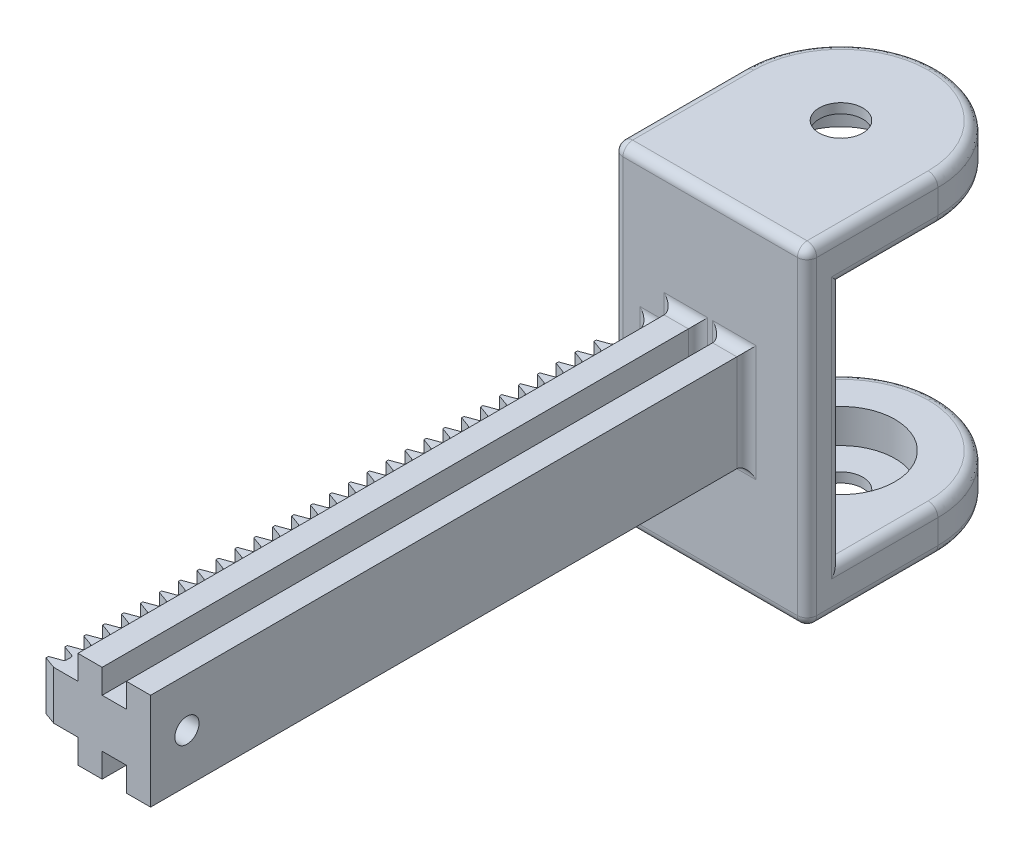
SolidWorks part; units mm, degrees
note: The reader was unsure of these and kept them because the rebuilt part matched: shared geometry of "Croquis4<4>".
ref_plane "Alzado" through (0, 0, 0) normal (1, 0, 0) x (0, 1, 0)
ref_plane "Planta" through (0, 0, 0) normal (0, 0, 1) x (0, 1, 0)
ref_plane "Vista lateral" through (0, 0, 0) normal (0, 1, 0) x (-1, 0, 0)
sketch "Croquis2" plane through (0, 0, 0) normal (0, 0, 1) x (0, 1, 0)
  line L0 (34, -20) -> (34, 20)
  line L1 (-34, -20) -> (34, -20)
  line L2 (-34, -20) -> (-34, 20)
  line L3 (-34, 20) -> (34, 20)
  line L5 (-34, -20) -> (34, 20) construction
  line L6 (-34, 20) -> (34, -20) construction
  point P0 (0, 0)
  point P1 (0, -20)
  point P13 (34, 0)
  dimension "D2" = 68
  dimension "D3" = 40
extrude "Saliente-Extruir1" add sketch "Croquis2" along normal blind 7
sketch "Croquis3" plane through (0, 0, 0) normal (0, 0, -1) x (1, 0, 0)
  line L0 (20, -34) -> (-20, -34) construction
  line L1 (20, 34) -> (-20, 34) construction
  line L2 (20, -34) -> (-20, -34)
  line L3 (20, 34) -> (-20, 34)
  line L4 (-20, 34) -> (-20, 25)
  line L5 (-20, 34) -> (-20, -34) construction
  line L6 (-20, 25) -> (20, 25)
  line L7 (20, 34) -> (20, -34) construction
  line L8 (20, 25) -> (20, 34)
  line L9 (20, -34) -> (20, -25)
  line L10 (20, -25) -> (-20, -25)
  line L11 (-20, -25) -> (-20, -34)
  dimension "D1" = 9
  dimension "D2" = 9
extrude "Saliente-Extruir2" add sketch "Croquis3" along normal blind 40
sketch "Croquis4" plane through (0, 25, 0) normal (0, -1, 0) x (1, 0, 0)
  line L0 (20, -20) -> (0, -20) construction
  line L1 (20, -40) -> (20, 0) construction
  line L2 (0, -20) -> (0, 0) construction
  circle A0 centre (0, -20) radius 11.15
  circle A1 centre (0, -20) radius 4.5
  dimension "D1" = 22.3
  dimension "D2" = 9
extrude "Cortar-Extruir1" cut sketch "Croquis4" against normal blind 7 and the other way offset from surface (57 mm away) 2 contours A1 | A0 A1 other way up to face at (0, -34, -16.5)
extrude "Cortar-Extruir2" cut sketch "Croquis4<4>" against normal up to next and the other way up to next contours A1
sketch "Croquis4<4>" plane through (0, 25, 0) normal (0, -1, 0) x (1, 0, 0) same geometry as "Croquis4"
sketch "Croquis5" plane through (0, 0, 7) normal (0, 0, 1) x (1, 0, 0)
  line L0 (-12.5, -5) -> (-7.5, -5)
  line L1 (7.5, -10) -> (2.5, -10)
  line L2 (7.5, -10) -> (7.5, 10)
  line L3 (7.5, 10) -> (2.5, 10)
  line L4 (-7.5, -10) -> (-7.5, -5)
  line L5 (7.5, -10) -> (-7.5, 10) construction
  line L6 (7.5, 10) -> (-7.5, -10) construction
  line L7 (-12.5, -5) -> (-12.5, 5)
  line L9 (-12.5, 5) -> (-7.5, 5)
  line L10 (-12.5, -5) -> (-7.5, 5) construction
  line L11 (-7.5, -5) -> (-12.5, 5) construction
  line L12 (-7.5, 5) -> (-7.5, 10)
  line L13 (-2.5, 10) -> (-7.5, 10)
  line L15 (-2.5, 10) -> (-2.5, 5)
  line L16 (-2.5, 5) -> (2.5, 5)
  line L17 (2.5, 10) -> (2.5, 5)
  line L18 (55, 0) -> (-55, 0) construction
  line L19 (2.5, -10) -> (2.5, -5)
  line L20 (-2.5, -5) -> (2.5, -5)
  line L21 (-2.5, -10) -> (-2.5, -5)
  line L22 (-2.5, -10) -> (-7.5, -10)
  point P0 (0, 0)
  point P5 (0, 5)
  point P7 (-10, 0)
  dimension "D1" = 20
  dimension "D2" = 15
  dimension "D3" = 5
  dimension "D4" = 10
  dimension "D5" = 5
  dimension "D6" = 5
extrude "Saliente-Extruir3" add sketch "Croquis5" along normal blind 123
sketch "Croquis8" plane through (0, 0, 0) normal (0, 1, 0) x (-1, 0, 0)
  line L0 (12.5, 130) -> (12.5, 7) construction
  line L1 (12.5, 130) -> (12.5, 7)
  line L2 (12.5, 130) -> (15, 129.0901)
  line L3 (15, 129.0901) -> (15, 128.6099)
  line L4 (15, 128.6099) -> (12.5, 127.7)
  line L5 (12.5, 127.7) -> (12.5, 126.1)
  line L6 (13.75, 128.155) -> (13.75, 129.545) construction
  line L7 (12.5, 126.9) -> (10.9627, 126.9) construction
  line L8 (12.5, 116) -> (12.5, 114.4)
  line L9 (12.5, 126.1) -> (15, 125.1901)
  line L10 (15, 125.1901) -> (15, 124.7099)
  line L11 (15, 124.7099) -> (12.5, 123.8)
  line L12 (12.5, 123.8) -> (12.5, 122.2)
  line L13 (13.75, 124.255) -> (13.75, 125.645) construction
  line L14 (15, 116.9099) -> (12.5, 116)
  line L15 (15, 117.3901) -> (15, 116.9099)
  line L16 (12.5, 118.3) -> (15, 117.3901)
  line L17 (12.5, 119.9) -> (12.5, 118.3)
  line L18 (15, 120.8099) -> (12.5, 119.9)
  line L19 (15, 121.2901) -> (15, 120.8099)
  line L20 (12.5, 122.2) -> (15, 121.2901)
  line L21 (12.5, 108.2) -> (12.5, 106.6)
  line L22 (15, 109.1099) -> (12.5, 108.2)
  line L23 (15, 109.5901) -> (15, 109.1099)
  line L24 (12.5, 110.5) -> (15, 109.5901)
  line L25 (12.5, 112.1) -> (12.5, 110.5)
  line L26 (15, 113.0099) -> (12.5, 112.1)
  line L27 (15, 113.4901) -> (15, 113.0099)
  line L28 (12.5, 114.4) -> (15, 113.4901)
  line L29 (12.5, 100.4) -> (12.5, 98.8)
  line L30 (15, 101.3099) -> (12.5, 100.4)
  line L31 (15, 101.7901) -> (15, 101.3099)
  line L32 (12.5, 102.7) -> (15, 101.7901)
  line L33 (12.5, 104.3) -> (12.5, 102.7)
  line L34 (15, 105.2099) -> (12.5, 104.3)
  line L35 (15, 105.6901) -> (15, 105.2099)
  line L36 (12.5, 106.6) -> (15, 105.6901)
  line L37 (12.5, 92.6) -> (12.5, 91)
  line L38 (15, 93.5099) -> (12.5, 92.6)
  line L39 (15, 93.9901) -> (15, 93.5099)
  line L40 (12.5, 94.9) -> (15, 93.9901)
  line L41 (12.5, 96.5) -> (12.5, 94.9)
  line L42 (15, 97.4099) -> (12.5, 96.5)
  line L43 (15, 97.8901) -> (15, 97.4099)
  line L44 (12.5, 98.8) -> (15, 97.8901)
  line L45 (12.5, 84.8) -> (12.5, 83.2)
  line L46 (15, 85.7099) -> (12.5, 84.8)
  line L47 (15, 86.1901) -> (15, 85.7099)
  line L48 (12.5, 87.1) -> (15, 86.1901)
  line L49 (12.5, 88.7) -> (12.5, 87.1)
  line L50 (15, 89.6099) -> (12.5, 88.7)
  line L51 (15, 90.0901) -> (15, 89.6099)
  line L52 (12.5, 91) -> (15, 90.0901)
  line L53 (12.5, 77) -> (12.5, 75.4)
  line L54 (15, 77.9099) -> (12.5, 77)
  line L55 (15, 78.3901) -> (15, 77.9099)
  line L56 (12.5, 79.3) -> (15, 78.3901)
  line L57 (12.5, 80.9) -> (12.5, 79.3)
  line L58 (15, 81.8099) -> (12.5, 80.9)
  line L59 (15, 82.2901) -> (15, 81.8099)
  line L60 (12.5, 83.2) -> (15, 82.2901)
  line L61 (12.5, 69.2) -> (12.5, 67.6)
  line L62 (15, 70.1099) -> (12.5, 69.2)
  line L63 (15, 70.5901) -> (15, 70.1099)
  line L64 (12.5, 71.5) -> (15, 70.5901)
  line L65 (12.5, 73.1) -> (12.5, 71.5)
  line L66 (15, 74.0099) -> (12.5, 73.1)
  line L67 (15, 74.4901) -> (15, 74.0099)
  line L68 (12.5, 75.4) -> (15, 74.4901)
  line L69 (12.5, 61.4) -> (12.5, 59.8)
  line L70 (15, 62.3099) -> (12.5, 61.4)
  line L71 (15, 62.7901) -> (15, 62.3099)
  line L72 (12.5, 63.7) -> (15, 62.7901)
  line L73 (12.5, 65.3) -> (12.5, 63.7)
  line L74 (15, 66.2099) -> (12.5, 65.3)
  line L75 (15, 66.6901) -> (15, 66.2099)
  line L76 (12.5, 67.6) -> (15, 66.6901)
  line L77 (12.5, 53.6) -> (12.5, 52)
  line L78 (15, 54.5099) -> (12.5, 53.6)
  line L79 (15, 54.9901) -> (15, 54.5099)
  line L80 (12.5, 55.9) -> (15, 54.9901)
  line L81 (12.5, 57.5) -> (12.5, 55.9)
  line L82 (15, 58.4099) -> (12.5, 57.5)
  line L83 (15, 58.8901) -> (15, 58.4099)
  line L84 (12.5, 59.8) -> (15, 58.8901)
  line L85 (12.5, 45.8) -> (12.5, 44.2)
  line L86 (15, 46.7099) -> (12.5, 45.8)
  line L87 (15, 47.1901) -> (15, 46.7099)
  line L88 (12.5, 48.1) -> (15, 47.1901)
  line L89 (12.5, 49.7) -> (12.5, 48.1)
  line L90 (15, 50.6099) -> (12.5, 49.7)
  line L91 (15, 51.0901) -> (15, 50.6099)
  line L92 (12.5, 52) -> (15, 51.0901)
  line L93 (12.5, 38) -> (12.5, 36.4)
  line L94 (15, 38.9099) -> (12.5, 38)
  line L95 (15, 39.3901) -> (15, 38.9099)
  line L96 (12.5, 40.3) -> (15, 39.3901)
  line L97 (12.5, 41.9) -> (12.5, 40.3)
  line L98 (15, 42.8099) -> (12.5, 41.9)
  line L99 (15, 43.2901) -> (15, 42.8099)
  line L100 (12.5, 44.2) -> (15, 43.2901)
  line L101 (12.5, 30.2) -> (12.5, 28.6)
  line L102 (15, 31.1099) -> (12.5, 30.2)
  line L103 (15, 31.5901) -> (15, 31.1099)
  line L104 (12.5, 32.5) -> (15, 31.5901)
  line L105 (12.5, 34.1) -> (12.5, 32.5)
  line L106 (15, 35.0099) -> (12.5, 34.1)
  line L107 (15, 35.4901) -> (15, 35.0099)
  line L108 (12.5, 36.4) -> (15, 35.4901)
  line L109 (12.5, 22.4) -> (12.5, 20.8)
  line L110 (15, 23.3099) -> (12.5, 22.4)
  line L111 (15, 23.7901) -> (15, 23.3099)
  line L112 (12.5, 24.7) -> (15, 23.7901)
  line L113 (12.5, 26.3) -> (12.5, 24.7)
  line L114 (15, 27.2099) -> (12.5, 26.3)
  line L115 (15, 27.6901) -> (15, 27.2099)
  line L116 (12.5, 28.6) -> (15, 27.6901)
  line L117 (12.5, 14.6) -> (12.5, 13)
  line L118 (15, 15.5099) -> (12.5, 14.6)
  line L119 (15, 15.9901) -> (15, 15.5099)
  line L120 (12.5, 16.9) -> (15, 15.9901)
  line L121 (12.5, 18.5) -> (12.5, 16.9)
  line L122 (15, 19.4099) -> (12.5, 18.5)
  line L123 (15, 19.8901) -> (15, 19.4099)
  line L124 (12.5, 20.8) -> (15, 19.8901)
  point P4 (15, 128.85)
  point P17 (15, 124.95)
  dimension "D3" = 2.5
  dimension "D1" = 1.25
  dimension "D5" = 1.6
  dimension "D2" = 70
  dimension "D4" = 70
  dimension "D6" = 70
  dimension "D7" = 3.9
extrude "Saliente-Extruir4" add sketch "Croquis8" along normal mid plane 10 contours L11 L10 L9 L1 | L4 L3 L2 L1 | L20 L1 L18 L19 | L16 L1 L14 L15 | L28 L1 L26 L27 | L24 L1 L22 L23 | L36 L1 L34 L35 | L32 L1 L30 L31 | L44 L1 L42 L43 | L40 L1 L38 L39 | L52 L1 L50 L51 | L48 L1 L46 L47 | L60 L1 L58 L59 | L56 L1 L54 L55 | L68 L1 L66 L67 | L64 L1 L62 L63 | L76 L1 L74 L75 | L72 L1 L70 L71 | L84 L1 L82 L83 | L80 L1 L78 L79 | L92 L1 L90 L91 | L88 L1 L86 L87 | L100 L1 L98 L99 | L96 L1 L94 L95 | L108 L1 L106 L107 | L104 L1 L102 L103 | L116 L1 L114 L115 | L112 L1 L110 L111 | L124 L1 L122 L123 | L120 L1 L118 L119
fillet "Redondeo1" radius 0.5 59 edges at (-12.5, 0, 14.6) (-12.5, 0, 16.9) (-12.5, 0, 18.5) (-12.5, 0, 20.8) (-12.5, 0, 24.7) (-12.5, 0, 22.4) (-12.5, 0, 26.3) (-12.5, 0, 28.6) (-12.5, 0, 30.2) (-12.5, 0, 32.5) (-12.5, 0, 34.1) (-12.5, 0, 36.4) (-12.5, 0, 38) (-12.5, 0, 40.3) (-12.5, 0, 44.2) (-12.5, 0, 41.9) (-12.5, 0, 45.8) (-12.5, 0, 48.1) (-12.5, 0, 49.7) (-12.5, 0, 52) (-12.5, 0, 55.9) (-12.5, 0, 53.6) (-12.5, 0, 57.5) (-12.5, 0, 59.8) (-12.5, 0, 61.4) (-12.5, 0, 63.7) (-12.5, 0, 65.3) (-12.5, 0, 67.6) (-12.5, 0, 69.2) (-12.5, 0, 71.5) (-12.5, 0, 73.1) (-12.5, 0, 75.4) (-12.5, 0, 77) (-12.5, 0, 79.3) (-12.5, 0, 80.9) (-12.5, 0, 83.2) (-12.5, 0, 84.8) (-12.5, 0, 87.1) (-12.5, 0, 88.7) (-12.5, 0, 91) (-12.5, 0, 92.6) (-12.5, 0, 94.9) (-12.5, 0, 96.5) (-12.5, 0, 98.8) (-12.5, 0, 100.4) (-12.5, 0, 102.7) (-12.5, 0, 104.3) (-12.5, 0, 106.6) (-12.5, 0, 108.2) (-12.5, 0, 110.5) (-12.5, 0, 112.1) (-12.5, 0, 114.4) (-12.5, 0, 116) (-12.5, 0, 118.3) (-12.5, 0, 119.9) (-12.5, 0, 122.2) (-12.5, 0, 123.8) (-12.5, 0, 126.1) (-12.5, 0, 127.7)
sketch "Croquis9" plane through (7.5, 0, 0) normal (1, 0, 0) x (0, 1, 0)
  line L0 (-10, 130) -> (10, 130) construction
  circle A0 centre (0, 122.5) radius 2.5
  circle A1 centre (0, 122.5) radius 4.5
  point P0 (0, 130)
  dimension "D1" = 5
  dimension "D3" = 2
  dimension "D2" = 7.5
extrude "Cortar-Extruir3" cut sketch "Croquis9" against normal blind 5 contours A0
fillet "Redondeo2" radius 20 4 edges at (20, -29.5, -40) (-20, -29.5, -40) (20, 29.5, -40) (-20, 29.5, -40)
fillet "Redondeo4" radius 2 38 edges at (20, 0, 0) (-7.5, 7.5, 7) (-10, 5, 7) (-12.5, 0, 7) (-10, -5, 7) (-7.5, -7.5, 7) (-5, -10, 7) (-2.5, -7.5, 7) (0, -5, 7) (2.5, -7.5, 7) (5, -10, 7) (7.5, 0, 7) (5, 10, 7) (2.5, 7.5, 7) (0, 5, 7) (-2.5, 7.5, 7) (-5, 10, 7) (-20, 0, 7) (0, 34, 7) (20, 0, 7) (0, -34, 7) (-20, 0, 0)
equation "\"D4@Croquis8\"=\"D2@Croquis8\""
equation "\"D6@Croquis8\"=\"D2@Croquis8\""
